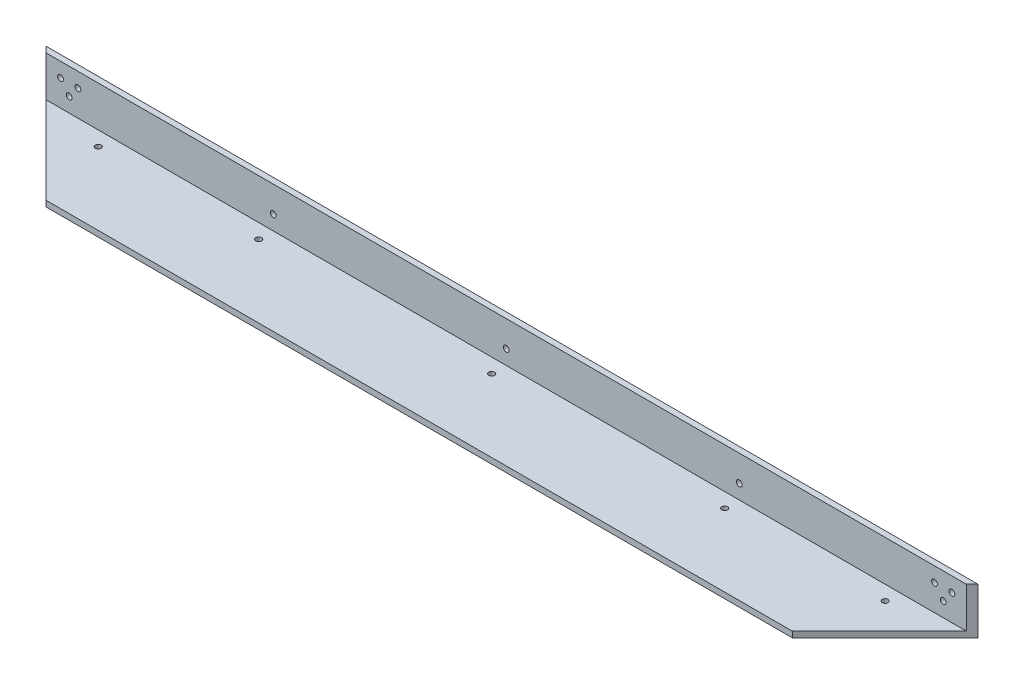
SolidWorks part; units mm, degrees
ref_plane "Front Plane" through (0, 0, 0) normal (0, 0, 1) x (1, 0, 0)
ref_plane "Top Plane" through (0, 0, 0) normal (0, 1, 0) x (1, 0, 0)
ref_plane "Right Plane" through (0, 0, 0) normal (1, 0, 0) x (0, 0, -1)
sketch "Sketch1" plane through (0, 0, 0) normal (1, 0, 0) x (0, 0, -1)
  line L0 (0, 0) -> (-50.8, 0)
  line L1 (-50.8, 0) -> (-50.8, 3.175)
  line L2 (-50.8, 3.175) -> (-3.175, 3.175)
  line L3 (-3.175, 3.175) -> (-3.175, 25.4)
  line L4 (-3.175, 25.4) -> (0, 25.4)
  line L5 (0, 25.4) -> (0, 0)
  dimension "LHeight" = 25.4
  dimension "LWidth" = 50.8
  dimension "LMaterialThickness" = 3.175
  dimension "D1" = 47.625
  dimension "D2" = 22.225
  dimension "D3" = 3.175
extrude "Boss-Extrude1" add sketch "Sketch1" along normal blind 510
chamfer "Chamfer6" distance 50.8 angle 45 1 edges at (510, 1.5875, 50.8)
chamfer "Chamfer7" distance 50.8 angle 45 1 edges at (0, 1.5875, 50.8)
sketch "FrontSideHoles-Sketch2" plane through (0, 0, 0) normal (0, 0, -1) x (-1, 0, 0)
  line L0 (0, 0) -> (0, 25.4) construction
  line L1 (-510, 0) -> (0, 0) construction
  line L2 (-510, 0) -> (-510, 25.4) construction
  circle A0 centre (-498.8875, 17.4625) radius 1.5875
  circle A1 centre (-489.3625, 17.4625) radius 1.5875
  circle A2 centre (-20.6375, 17.4625) radius 1.5875
  circle A3 centre (-11.1125, 17.4625) radius 1.5875
  circle A5 centre (-15.875, 11.1125) radius 1.5875
  circle A6 centre (-494.125, 11.1125) radius 1.5875
  circle A8 centre (-382.5, 11.1125) radius 1.5875
  circle A9 centre (-255, 11.1125) radius 1.5875
  circle A10 centre (-127.5, 11.1125) radius 1.5875
  dimension "D5" = 3.175
  dimension "D1" = 11.1125
  dimension "D2" = 20.6375
  dimension "D3" = 11.1125
  dimension "D4" = 20.6375
  dimension "D6" = 7.9375
  dimension "D8" = 127.5
  dimension "D9" = 127.5
  dimension "D10" = 127.5
  dimension "D7" = 11.1125
  dimension "D11" = 15.875
  dimension "D12" = 15.875
extrude "FrontSideHoles-Cut-Extrude2" cut sketch "FrontSideHoles-Sketch2" against normal through all
sketch "BottomHoles-Sketch2" plane through (0, 0, 0) normal (0, -1, 0) x (1, 0, 0)
  line L0 (510, 0) -> (0, 0) construction
  circle A0 centre (39.6875, 11.1125) radius 1.5875
  circle A1 centre (470.3125, 11.1125) radius 1.5875
  circle A2 centre (127.5, 11.1125) radius 1.5875
  circle A3 centre (255, 11.1125) radius 1.5875
  circle A4 centre (382.5, 11.1125) radius 1.5875
  dimension "D1" = 11.1125
  dimension "D4" = 3.175
  dimension "D2" = 39.6875
  dimension "D3" = 39.6875
  dimension "D5" = 127.5
  dimension "D6" = 127.5
  dimension "D7" = 127.5
extrude "BottomHoles-Cut-Extrude1" cut sketch "BottomHoles-Sketch2" against normal through all
equation "\"LowerRailWidth\"= 2.00in"
equation "\"LowerRailHeight\"= 1.00in"
equation "\"RailThickness\"= .125in'Spec"
equation "\"SideRailHoleX1FromSide\"= \"HoleOffsetFromSide\""
equation "\"SideRailHoleX2FromSide\"= \"VSWidth\" - \"HoleOffsetFromEdge\" - \"RailThickness\"'Equals 20.6375"
equation "\"SideRailHoleY1FromEdge\"= \"HoleOffsetFromEdge\""
equation "\"FrontBackRailLength\"= 510mm"
equation "\"VSWidth\"= 1.25in'Spec"
equation "\"HoleOffsetFromEdge\"= \"RailThickness\" * 2.5"
equation "\"HoleOffsetFromSide\"= \"RailThickness\" * 3.5"
equation "\"SideRailHoleY2FromSide\"= \"HoleOffsetFromSide\""
equation "\"FasteningHoleDiameter\"= .125in"
equation "\"D1@Boss-Extrude1\"=\"FrontBackRailLength\""
equation "\"D1@Chamfer6\"=\"LowerRailWidth\""
equation "\"D1@Chamfer7\"=\"LowerRailWidth\""
equation "\"D1@FrontSideHoles-Sketch2\" = \"SideRailHoleX1FromSide\""
equation "\"D2@FrontSideHoles-Sketch2\" = \"SideRailHoleX2FromSide\""
equation "\"D3@FrontSideHoles-Sketch2\" = \"SideRailHoleX1FromSide\""
equation "\"D4@FrontSideHoles-Sketch2\" = \"SideRailHoleX2FromSide\""
equation "\"D5@FrontSideHoles-Sketch2\" = \"FasteningHoleDiameter\""
equation "\"D6@FrontSideHoles-Sketch2\" = \"SideRailHoleY1FromEdge\""
equation "\"LHeight@Sketch1\"=\"LowerRailHeight\""
equation "\"LWidth@Sketch1\"=\"LowerRailWidth\""
equation "\"LowerCornerBlockWidth\"= \"LowerRailWidth\" - \"RailThickness\" * 2'Room for left front stepper"
equation "\"D1@BottomHoles-Sketch2\"=\"LowerCornerBlockY1FromSide\""
equation "\"D2@BottomHoles-Sketch2\"=\"CornerEnclosureOffset\""
equation "\"D3@BottomHoles-Sketch2\"=\"CornerEnclosureOffset\""
equation "\"D4@BottomHoles-Sketch2\" = \"FasteningHoleDiameter\""
equation "\"CornerEnclosureOffset\"= \"LowerCornerBlockWidth\" - \"HoleOffsetFromEdge\" + \"RailThickness\""
equation "\"LowerCornerBlockY1FromSide\"= \"HoleOffsetFromSide\""
equation "\"FrontOrBackEnclosureOffsets\"= \"FrontBackRailLength\" / 4"
equation "\"D5@BottomHoles-Sketch2\"=\"FrontOrBackEnclosureOffsets\""
equation "\"D6@BottomHoles-Sketch2\"=\"FrontOrBackEnclosureOffsets\""
equation "\"D7@BottomHoles-Sketch2\"=\"FrontOrBackEnclosureOffsets\""
equation "\"D8@FrontSideHoles-Sketch2\"=\"FrontOrBackEnclosureOffsets\""
equation "\"D9@FrontSideHoles-Sketch2\"=\"FrontOrBackEnclosureOffsets\""
equation "\"D10@FrontSideHoles-Sketch2\"=\"FrontOrBackEnclosureOffsets\""
equation "\"D7@FrontSideHoles-Sketch2\"=\"SideRailHoleY2FromSide\""
equation "\"VSMidSideRailHoleXFromSideToCenter\"= \"RailThickness\" * 6"
equation "\"D11@FrontSideHoles-Sketch2\"=\"VSMidSideRailHoleXFromSideToCenter\" - \"RailThickness\""
equation "\"D12@FrontSideHoles-Sketch2\"=\"VSMidSideRailHoleXFromSideToCenter\" - \"RailThickness\""
